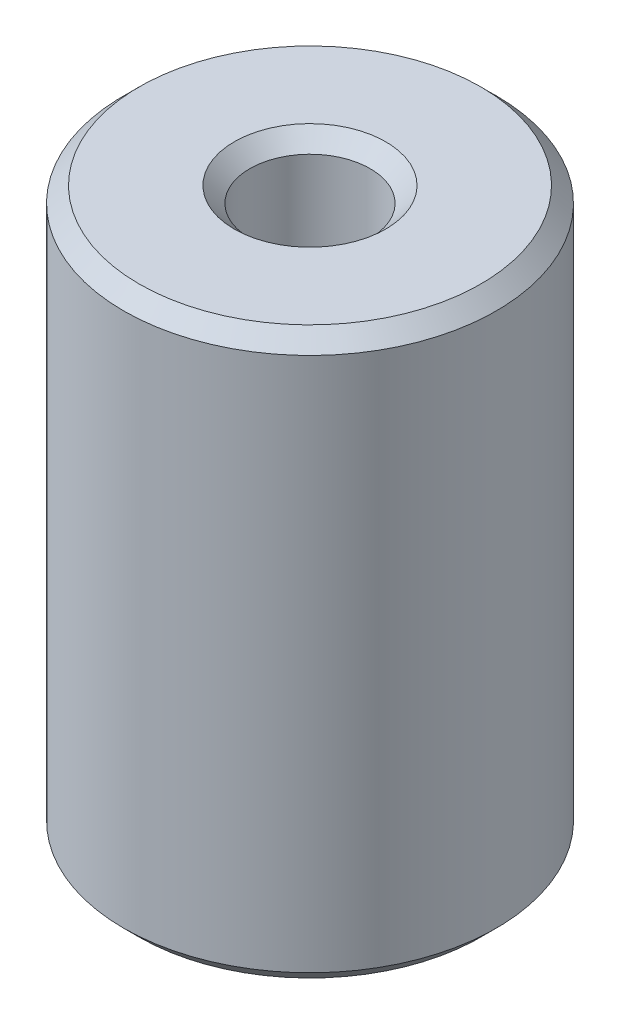
SolidWorks part; units mm, degrees
ref_plane "Front Plane" through (0, 0, 0) normal (0, 0, 1) x (1, 0, 0)
ref_plane "Top Plane" through (0, 0, 0) normal (0, 1, 0) x (1, 0, 0)
ref_plane "Right Plane" through (0, 0, 0) normal (1, 0, 0) x (0, 0, -1)
sketch "Sketch1" plane through (0, 0, 0) normal (0, 1, 0) x (1, 0, 0)
  circle A0 centre (0, 0) radius 5
  dimension "SLEEVE_OD" = 10
extrude "Boss-Extrude1" add sketch "Sketch1" along normal blind 15.1792
sketch "Sketch2" plane through (0, 0, 0) normal (0, 1, 0) x (1, 0, 0)
  circle A0 centre (0, 0) radius 1.6154
  dimension "BORE_D" = 3.2308
extrude "Cut-Extrude1" cut sketch "Sketch2" along normal through all
chamfer "Chamfer1" distance 0.4166 angle 45 4 edges at (0, 15.1792, 1.6154) (0, 0, 1.6154) (0, 0, 5) (0, 15.1792, 5)
